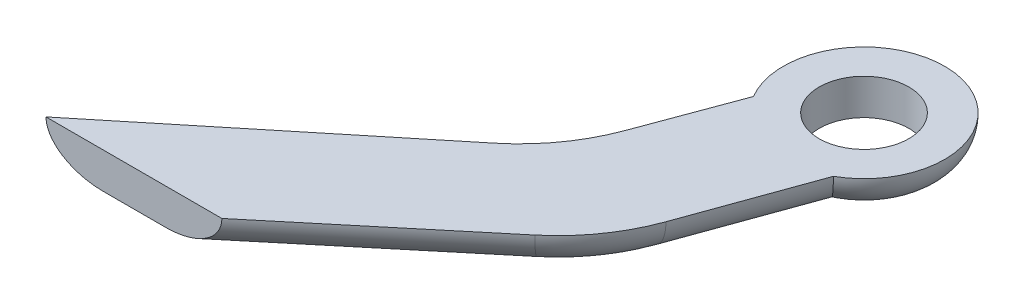
SolidWorks part; units mm, degrees
ref_plane "Front" through (0, 0, 0) normal (0, 0, 1) x (1, 0, 0)
ref_plane "Top" through (0, 0, 0) normal (0, 1, 0) x (1, 0, 0)
ref_plane "Right" through (0, 0, 0) normal (1, 0, 0) x (0, 0, -1)
sketch "Sketch1" plane through (0, 0, 0) normal (0, 1, 0) x (1, 0, 0)
  line L0 (4.7344, 4.3375) -> (-11.1234, -8.6004)
  line L1 (-11.1234, -8.6004) -> (-1.3192, -8.6004)
  line L2 (-1.3192, -8.6004) -> (10.2971, 1.0617)
  line L3 (10.2971, 1.0617) -> (13.6935, 10.4802)
  line L6 (-1.3192, -8.6004) -> (-1.3192, 14.3996) construction
  line L7 (-1.3192, 14.3996) -> (6.9826, 14.3996) construction
  line L9 (7.6119, 12.1045) -> (4.7344, 4.3375)
  circle A0 centre (11.4826, 14.3996) radius 2.5
  arc A1 (13.6935, 10.4802) -> (7.6119, 12.1045) centre (11.4826, 14.3996) ccw
  circle A2 centre (11.4826, 14.3996) radius 4.5 construction
  dimension "D1" = 2
extrude "Boss-Extrude1" add sketch "Sketch1" along normal blind 2
fillet "Fillet1" radius 10 1 edges at (10.2971, 1, -1.0617)
fillet "Fillet2" radius 10 1 edges at (4.7344, 1, -4.3375)
fillet "Fillet3" radius 2 6 edges at (6.6461, 0, -9.4976) (4.4383, 0, -4.5492) (12.4564, 0, -7.0496) (9.9999, 0, -1.2701) (-4.2493, 0, 2.992) (3.4439, 0, 4.6385)
fillet "Fillet4" radius 2 1 edges at (12.7443, 0, -18.7191)
